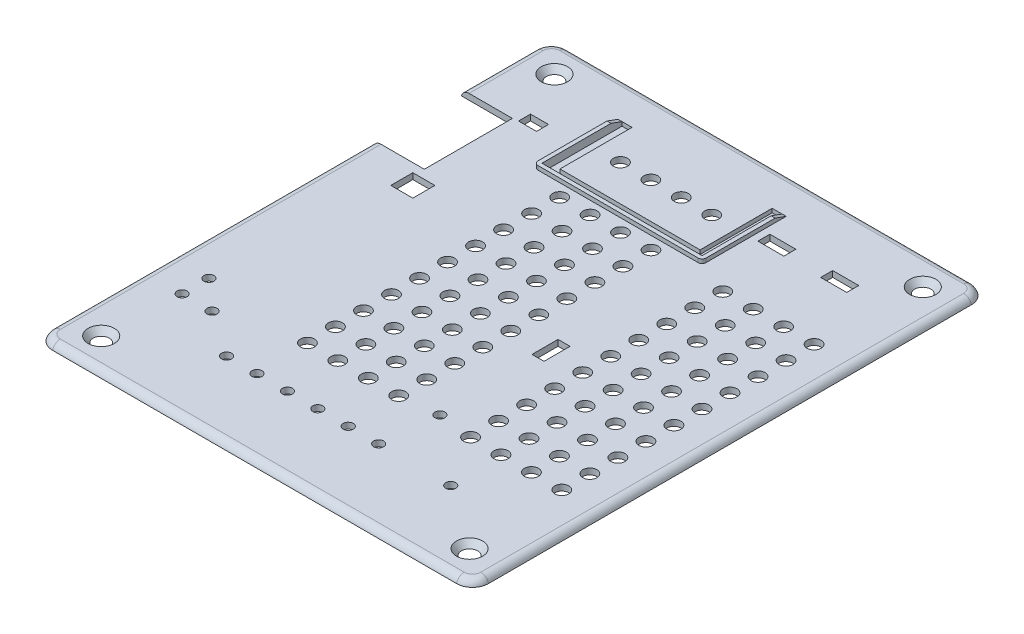
SolidWorks part; units mm, degrees
ref_plane "Přední rovina" through (0, 0, 0) normal (0, 0, 1) x (1, 0, 0)
ref_plane "Horní rovina" through (0, 0, 0) normal (0, 1, 0) x (1, 0, 0)
ref_plane "Pravá rovina" through (0, 0, 0) normal (1, 0, 0) x (0, 0, -1)
sketch "Skica1" plane through (0, 0, 0) normal (0, 1, 0) x (1, 0, 0)
  line L1 (-54.445, -64.3) -> (54.445, -64.3)
  line L2 (-54.445, -64.3) -> (-54.445, 64.3)
  line L3 (-54.445, 64.3) -> (54.445, 64.3)
  line L4 (54.445, -64.3) -> (54.445, 64.3)
  line L5 (-54.445, -64.3) -> (54.445, 64.3) construction
  line L6 (-54.445, 64.3) -> (54.445, -64.3) construction
  point P0 (0, 0)
  dimension "D1" = 108.89
  dimension "D2" = 128.6
extrude "Přidat vysunutím1" add sketch "Skica1" along normal blind 1.5
fillet "Zaoblit1" radius 4 4 edges at (54.445, 0.75, -64.3) (54.445, 0.75, 64.3) (-54.445, 0.75, -64.3) (-54.445, 0.75, 64.3)
fillet "Zaoblit2" radius 2 8 edges at (53.2734, 1.5, 63.1284) (0, 1.5, 64.3) (-53.2734, 1.5, 63.1284) (-54.445, 1.5, 0) (-53.2734, 1.5, -63.1284) (0, 1.5, -64.3) (53.2734, 1.5, -63.1284) (54.445, 1.5, 0)
sketch "Skica2" plane through (0, 0, 0) normal (0, -1, 0) x (1, 0, 0)
  line L0 (0, 68.8192) -> (0, -71.6902) construction
  line L1 (-80.8942, 0) -> (91.0271, 0) construction
  circle A0 centre (-46, 56.6) radius 1.6
  dimension "D1" = 3.2
  dimension "D2" = 46
  dimension "D3" = 56.6
extrude "Odebrat vysunutím1" cut sketch "Skica2" against normal blind 3
pattern_linear "LinPole1" count 2 spacing 113.2 along (0, 0, -1) count 2 spacing 92 along (1, 0, 0) of "Odebrat vysunutím1"
chamfer "Zkosení1" distance 2 angle 40 4 edges at (46, 1.5, 55) (46, 1.5, -58.2) (-46, 1.5, -58.2) (-46, 1.5, 55) first distance on face at (46, 0, 55) first distance on face at (46, 0, -58.2) first distance on face at (-46, 0, -58.2) first distance on face at (-46, 0, 55)
sketch "Skica3" plane through (0, 1.5, 0) normal (0, 1, 0) x (1, 0, 0)
  line L3 (-50, -50) -> (50, -50) construction
  line L4 (-50, -50) -> (-50, 50) construction
  line L5 (-50, 50) -> (50, 50) construction
  line L6 (50, -50) -> (50, 50) construction
  line L7 (-50, -50) -> (50, 50) construction
  line L8 (-50, 50) -> (50, -50) construction
  circle A0 centre (44.83, -32.38) radius 1.75
  circle A1 centre (4.08, -32.38) radius 1.75
  circle A2 centre (4.08, 45.8) radius 1.75
  point P7 (0, 0)
  dimension "D2" = 3.5
  dimension "D6" = 3.5
  dimension "D11" = 3.5
  dimension "D1" = 5.17
  dimension "D3" = 17.62
  dimension "D4" = 100
  dimension "D5" = 100
  dimension "D7" = 45.92
  dimension "D8" = 17.62
  dimension "D9" = 45.92
  dimension "D10" = 4.2
extrude "Odebrat vysunutím3" cut sketch "Skica3" against normal blind 4 contours A0 region at (44.83, 1.5, 32.38)
pattern_linear "LinPole3" count 10 spacing 7 along (0, 0, -1) count 4 spacing 7.6 along (-1, 0, 0) of "Odebrat vysunutím3"
extrude "Odebrat vysunutím4" cut sketch "Skica3<3>" against normal blind 4 contours A1 region at (4.08, 1.5, 32.38)
sketch "Skica3<3>" plane through (0, 1.5, 0) normal (0, 1, 0) x (1, 0, 0) same geometry as "Skica3"
pattern_linear "LinPole4" count 10 spacing 7 along (0, 0, -1) count 4 spacing 7.6 along (-1, 0, 0) of "Odebrat vysunutím4"
extrude "Odebrat vysunutím5" cut sketch "Skica3<4>" against normal blind 10
sketch "Skica3<4>" plane through (0, 1.5, 0) normal (0, 1, 0) x (1, 0, 0) same geometry as "Skica3"
pattern_linear "LinPole5" count 4 spacing 7.6 along (-1, 0, 0) of "Odebrat vysunutím5"
sketch "Skica4" plane through (0, 1.5, 0) normal (0, 1, 0) x (1, 0, 0)
  line L1 (-50, -50) -> (50, -50) construction
  line L2 (-50, -50) -> (-50, 50) construction
  line L3 (-50, 50) -> (50, 50) construction
  line L4 (50, -50) -> (50, 50) construction
  line L5 (-50, -50) -> (50, 50) construction
  line L6 (-50, 50) -> (50, -50) construction
  line L7 (15.5, 48.9) -> (22, 48.9)
  line L8 (15.5, 48.9) -> (15.5, 45.9)
  line L9 (15.5, 45.9) -> (22, 45.9)
  line L10 (22, 48.9) -> (22, 45.9)
  line L11 (15.5, 48.9) -> (22, 45.9) construction
  line L12 (15.5, 45.9) -> (22, 48.9) construction
  line L13 (31.2, 48.9) -> (37.7, 48.9)
  line L14 (31.2, 48.9) -> (31.2, 45.9)
  line L15 (31.2, 45.9) -> (37.7, 45.9)
  line L16 (37.7, 48.9) -> (37.7, 45.9)
  line L17 (31.2, 48.9) -> (37.7, 45.9) construction
  line L18 (31.2, 45.9) -> (37.7, 48.9) construction
  line L19 (11.8, -0.3) -> (14.8, -0.3)
  line L20 (11.8, -0.3) -> (11.8, -6.8)
  line L21 (11.8, -6.8) -> (14.8, -6.8)
  line L22 (14.8, -0.3) -> (14.8, -6.8)
  line L23 (11.8, -0.3) -> (14.8, -6.8) construction
  line L24 (11.8, -6.8) -> (14.8, -0.3) construction
  circle A0 centre (13.38, -31.4) radius 1.25
  circle A2 centre (30, -45.3) radius 1.25
  circle A3 centre (-45, -37.4) radius 1.25
  circle A4 centre (-45, -30.7) radius 1.25
  circle A5 centre (-37.52, -37.4) radius 1.25
  point P0 (0, 0)
  point P6 (18.75, 47.4)
  point P11 (34.45, 47.4)
  point P16 (13.3, -3.55)
  point P21 (13.3, -0.3)
  dimension "D13" = 2.5
  dimension "D16" = 12.48
  dimension "D17" = 2.5
  dimension "D23" = 2.5
  dimension "D24" = 2.5
  dimension "D25" = 2.5
  dimension "D1" = 100
  dimension "D2" = 100
  dimension "D3" = 3
  dimension "D4" = 6.5
  dimension "D5" = 1.1
  dimension "D6" = 1.1
  dimension "D7" = 12.3
  dimension "D8" = 28
  dimension "D9" = 35.2
  dimension "D10" = 50.3
  dimension "D11" = 36.62
  dimension "D12" = 18.6
  dimension "D14" = 5
  dimension "D15" = 5
  dimension "D18" = 20
  dimension "4,5" = 4.7
  dimension "D20" = 80.7
  dimension "D21" = 87.4
  dimension "D22" = 87.4
extrude "Odebrat vysunutím6" cut sketch "Skica4" against normal blind 10
sketch "Skica5" plane through (0, 1.5, 0) normal (0, 1, 0) x (1, 0, 0)
  line L1 (-50, 50) -> (50, 50) construction
  line L2 (-50, 50) -> (-50, -50) construction
  line L3 (-50, -50) -> (50, -50) construction
  line L4 (50, 50) -> (50, -50) construction
  line L5 (-50, 50) -> (50, -50) construction
  line L6 (-50, -50) -> (50, 50) construction
  circle A0 centre (-26, -45.3) radius 1.25
  point P0 (0, 0)
  dimension "D5" = 2.5
  dimension "D1" = 100
  dimension "D2" = 100
  dimension "D3" = 4.7
  dimension "D4" = 76
extrude "Odebrat vysunutím7" cut sketch "Skica5" against normal blind 10
pattern_linear "LinPole6" count 6 spacing 7.6 along (1, 0, 0) of "Odebrat vysunutím7"
sketch "Skica6" plane through (0, 1.5, 0) normal (0, 1, 0) x (1, 0, 0)
  line L1 (-42.39, 17.62) -> (-36.89, 17.62)
  line L2 (-42.39, 17.62) -> (-42.39, 12.12)
  line L3 (-42.39, 12.12) -> (-36.89, 12.12)
  line L4 (-36.89, 17.62) -> (-36.89, 12.12)
  line L5 (-42.39, 17.62) -> (-36.89, 12.12) construction
  line L6 (-42.39, 12.12) -> (-36.89, 17.62) construction
  line L7 (-41.7, 41.8) -> (-63.2133, 41.8)
  line L8 (-41.7, 41.8) -> (-41.7, 19.8)
  line L9 (-41.7, 19.8) -> (-63.2133, 19.8)
  line L10 (-63.2133, 41.8) -> (-63.2133, 19.8)
  line L11 (-41.7, 41.8) -> (-63.2133, 19.8) construction
  line L12 (-41.7, 19.8) -> (-63.2133, 41.8) construction
  line L14 (-50, 50) -> (50, 50) construction
  line L15 (-50, 50) -> (-50, -50) construction
  line L16 (-50, -50) -> (50, -50) construction
  line L17 (50, 50) -> (50, -50) construction
  line L18 (-50, 50) -> (50, -50) construction
  line L19 (-50, -50) -> (50, 50) construction
  line L20 (-40.37, 45) -> (-35.87, 45)
  line L21 (-40.37, 45) -> (-40.37, 42)
  line L22 (-40.37, 42) -> (-35.87, 42)
  line L23 (-35.87, 45) -> (-35.87, 42)
  line L24 (-40.37, 45) -> (-35.87, 42) construction
  line L25 (-40.37, 42) -> (-35.87, 45) construction
  point P0 (-39.64, 14.87)
  point P5 (-52.4567, 30.8)
  point P12 (0, 0)
  point P18 (-52.4567, 41.8)
  point P20 (-38.12, 43.5)
  dimension "D1" = 100
  dimension "D2" = 100
  dimension "D3" = 10.36
  dimension "D4" = 35.13
  dimension "D5" = 5.5
  dimension "D6" = 8.2
  dimension "D7" = 30.2
  dimension "D8" = 8.3
  dimension "D9" = 6.5
  dimension "D10" = 11.88
  dimension "D11" = 4.5
  dimension "D12" = 3
extrude "Odebrat vysunutím8" cut sketch "Skica6" against normal blind 10 contours L4 L1 L2 L3 | L23 L20 L21 L22 | L7 L10 L9 L8 region at (-39.64, 1.5, -14.87) region at (-38.12, 1.5, -43.5)
sketch "Skica7" plane through (0, 1.5, 0) normal (0, 1, 0) x (1, 0, 0)
  line L1 (-24.82, 36.8) -> (10.18, 36.8)
  line L2 (-24.82, 36.8) -> (-24.82, 34.8)
  line L3 (-24.82, 34.8) -> (10.18, 34.8)
  line L4 (10.18, 36.8) -> (10.18, 34.8)
  line L5 (-27.32, 54.8) -> (-24.82, 54.8)
  line L6 (-27.32, 54.8) -> (-27.32, 34.8)
  line L7 (-27.32, 34.8) -> (-24.82, 34.8)
  line L8 (-24.82, 54.8) -> (-24.82, 34.8)
  line L9 (12.68, 54.8) -> (10.18, 54.8)
  line L10 (12.68, 54.8) -> (12.68, 34.8)
  line L11 (12.68, 34.8) -> (10.18, 34.8)
  line L12 (10.18, 54.8) -> (10.18, 34.8)
  circle A0 centre (-11.12, 45.8) radius 1.75 construction
  circle A1 centre (-18.72, 45.8) radius 1.75 construction
  dimension "D2" = 9
  dimension "D6" = 2
  dimension "D1" = 35
  dimension "D3" = 20
  dimension "D4" = 2.5
  dimension "D5" = 6.1
extrude "Odebrat vysunutím9" cut sketch "Skica7" against normal blind 1 contours L4 L1 L2 L3 | L8 L5 L6 L7 L2 | L9 L12 L4 L11 L10 region at (-7.32, 1.5, -35.8) region at (-26.07, 1.5, -44.8) region at (11.43, 1.5, -44.8)
sketch "Skica8" plane through (0, 1.5, 0) normal (0, 1, 0) x (1, 0, 0)
  line L0 (-27.32, 54.8) -> (-27.32, 34.8)
  line L1 (-27.32, 34.8) -> (12.68, 34.8)
  line L2 (12.68, 34.8) -> (12.68, 54.8)
  line L3 (12.68, 54.8) -> (13.68, 54.8)
  line L4 (13.68, 54.8) -> (13.68, 33.8)
  line L5 (13.68, 33.8) -> (-28.32, 33.8)
  line L6 (-28.32, 33.8) -> (-28.32, 54.8)
  line L7 (-28.32, 54.8) -> (-27.32, 54.8)
  point P11 (0, 0)
  point P14 (0, 0)
  dimension "D1" = 1
  dimension "D2" = 1
extrude "Přidat vysunutím2" add sketch "Skica8" along normal blind 1
chamfer "Zkosení2" distance 1 angle 70 2 edges at (-27.82, 2.5, -54.8) (13.18, 2.5, -54.8) first distance on face at (-27.82, 2, -54.8) first distance on face at (13.18, 2, -54.8)
fillet "Zaoblit3" radius 1 2 edges at (-28.32, 2, -33.8) (13.68, 2, -33.8)
